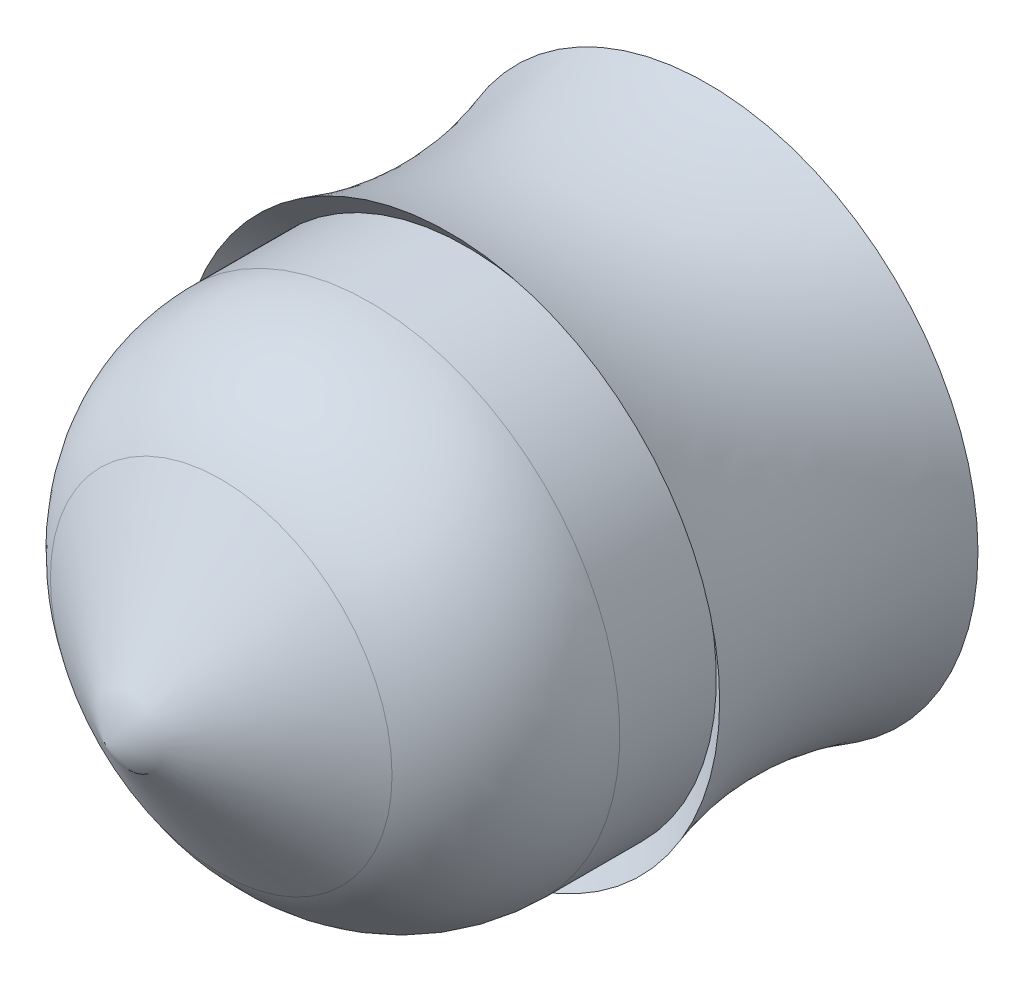
SolidWorks part; units mm, degrees
material "PE Vysoká hustota"
ref_plane "Horní rovina" through (0, 0, 0) normal (0, 0, 1) x (1, 0, 0)
ref_plane "Přední rovina" through (0, 0, 0) normal (0, 1, 0) x (1, 0, 0)
ref_plane "Pravá rovina" through (0, 0, 0) normal (1, 0, 0) x (0, 0, -1)
sketch "Skica1" plane through (0, 0, 0) normal (0, 0, 1) x (1, 0, 0)
  circle A0 centre (0, 0) radius 7.85
  dimension "D1" = 15.7
extrude "Přidat vysunutím1" add sketch "Skica1" along normal blind 7.5
sketch "Skica2" plane through (0, 0, 0) normal (0, 1, 0) x (1, 0, 0)
  line L0 (-7.85, -7.5) -> (7.85, -7.5) construction
  line L1 (-7.85, -7.5) -> (7.85, -7.5) construction
  line L2 (7.85, 0) -> (-7.85, 0) construction
  line L3 (7.85, 0) -> (-7.85, 0) construction
  line L4 (0, -14.5059) -> (0, 3.9252) construction
  line L5 (-7.85, -7.5) -> (-7.85, 0)
  arc A0 (-7.85, -7.5) -> (-7.85, 0) centre (-19.249, -3.75) ccw
  point P9 (-7.85, -3.75)
  dimension "D1" = 12
revolve "Odebrat rotací1" cut sketch "Skica2" angle 360 about L4
sketch "Skica4" plane through (0, 0, 0) normal (0, 1, 0) x (1, 0, 0)
  line L0 (-7.85, -7.5) -> (7.85, -7.5) construction
  line L1 (-7.85, -7.5) -> (7.85, -7.5) construction
  line L2 (0, 0) -> (0, -17.5) construction
  line L3 (0, -7.5) -> (-7.25, -7.5)
  line L4 (-7.25, -7.5) -> (-7.25, -9.8)
  line L5 (0, -17.5) -> (-4.961, -14.1254)
  line L6 (0, -17.5) -> (0, -7.5)
  arc A0 (-4.961, -14.1254) -> (-7.25, -9.8) centre (-2.0188, -9.8) cw
  dimension "D1" = 7.25
  dimension "D2" = 2.3
  dimension "D3" = 10
  dimension "D4" = 6
revolve "Rotovat1" add sketch "Skica4" angle 360 about L2
sketch "Skica5" plane through (0, 0, 0) normal (0, 1, 0) x (1, 0, 0)
  line L0 (-7.85, -7.5) -> (7.85, -7.5) construction
  line L1 (-7.85, -7.5) -> (7.85, -7.5) construction
  line L2 (-7.25, -7.5) -> (7.25, -7.5) construction
  line L3 (-7.25, -7.5) -> (7.25, -7.5) construction
  line L4 (-7.25, -7.5) -> (-7.25, -6.9965)
  line L5 (-7.25, -6.9965) -> (-7.85, -7.5)
  line L6 (-7.85, -7.5) -> (-7.25, -7.5)
  line L7 (0, 0) -> (0, -20.2146) construction
  dimension "D1" = 40
revolve "Odebrat rotací2" cut sketch "Skica5" angle 360 about L7
shell "Skořepina1" thickness 0.8 removed face at (7.85, 0, 0)
sketch "Skica6" plane through (0, 0, 0) normal (0, 0, 1) x (1, 0, 0)
  circle A0 centre (0, 0) radius 2
  dimension "D1" = 4
extrude "Přidat vysunutím2" add sketch "Skica6" along normal up to next from offset 9
sketch "Skica7" plane through (0, 0, 9) normal (0, 0, -1) x (-1, 0, 0)
  circle A0 centre (0, 0) radius 1
  dimension "D1" = 2
extrude "Odebrat vysunutím1" cut sketch "Skica7" against normal up to surface (6.8522 mm away) up to face at (-4.5111, 0, 13.4639)
sketch "Skica8" plane through (0, 0, 0) normal (0, 0, 1) x (1, 0, 0)
  line L0 (0, 0) -> (8.9804, 0) construction
  line L11 (1.9596, 0.4) -> (6.4376, 0.4)
  line L13 (1.9596, 0.4) -> (1.9596, -0.4) construction
  line L14 (1.9596, -0.4) -> (6.4376, -0.4)
  line L15 (6.4376, 0.4) -> (6.4376, -0.4) construction
  line L16 (1.9596, 0.4) -> (6.4376, -0.4) construction
  line L17 (1.9596, -0.4) -> (6.4376, 0.4) construction
  arc A0 (1.9596, -0.4) -> (1.9596, 0.4) centre (0, 0) ccw
  circle A4 centre (0, 0) radius 6.45 construction
  circle A7 centre (0, 0) radius 2 construction
  arc A8 (6.4376, -0.4) -> (6.4376, 0.4) centre (0, 0) ccw
  circle A12 centre (0, 0) radius 6.45 construction
  circle A13 centre (0, 0) radius 2 construction
  point P0 (4.1986, 0)
  dimension "D1" = 0.8
extrude "Přidat vysunutím7" add sketch "Skica8" along normal up to next from surface starting at face at (-1, 0, 9)
pattern_circular "Kruhové pole1" count 4 over 360 about axis through (0, 0, 9) along (0, 0, -1) of "Přidat vysunutím7"
sketch "Skica11" plane through (0, 0, 0) normal (0, 1, 0) x (1, 0, 0)
  line L0 (6.5376, -9.8) -> (6.5376, -9)
  line L3 (6.4376, -9.8) -> (6.4376, -9)
  line L4 (1.9596, -9) -> (1.9596, -15.172)
  line L5 (6.4376, -9) -> (1.9596, -9)
  line L6 (6.4376, -9.8) -> (6.4376, -9) construction
  line L7 (1.9596, -9) -> (1.9596, -15.172) construction
  line L8 (6.4376, -9) -> (1.9596, -9) construction
  line L9 (1.8596, -8.9) -> (1.8596, -15.36) construction
  line L10 (1.9596, -15.172) -> (4.4933, -13.4639) construction
  line L11 (1.8596, -15.36) -> (4.5493, -13.5467) construction
  line L12 (6.5376, -8.9) -> (1.8596, -8.9) construction
  line L13 (3.4596, -9) -> (6.1319, -11.6723)
  line L14 (3.4596, -9) -> (6.5376, -9)
  line L15 (6.5376, -9.8) -> (6.5376, -8.9) construction
  line L16 (0, 0) -> (0, -20.9939) construction
  spline S0 degree 1 poles (4.5493, -13.5467) (6.5376, -9.8) knots 0 0 1 1 construction
  spline S2 degree 3 poles (336.093, 3949.9235) (-368.0004, 250.9513) (-19.2767, -40.1177) (5.5441, -12.4898) (5.754, -12.1891) (6.0058, -11.7144) (6.08, -11.5514) (6.2088, -11.2154) (6.2636, -11.0414) (20.7742, 47.3659) (-1167.0022, 255.6626) (-3935.2453, 661.2338) knots -25.369542 -25.369542 -25.369542 -25.369542 0.25 0.25 0.5 0.5 0.625 0.625 0.75 0.75 42.34033 42.34033 42.34033 42.34033 only from (4.4933, -13.4639) to (6.4376, -9.8)
  spline S3 degree 3 poles (-2399.3678, 3177.3492) (2150.9174, -3378.5601) (-2142.0867, 3351.3669) (2407.3747, -3204.4617) knots -75.228616 -75.228616 -75.228616 -75.228616 77.085566 77.085566 77.085566 77.085566 only from (1.9596, -15.172) to (4.4933, -13.4639)
  spline S4 degree 3 poles (4.4933, -13.4639) (4.7936, -13.2604) (5.0644, -13.0237) (5.5441, -12.4898) (5.754, -12.1891) (6.0058, -11.7144) (6.08, -11.5514) (6.2088, -11.2154) (6.2636, -11.0414) (6.3941, -10.5163) (6.4376, -10.1609) (6.4376, -9.8) knots 0 0 0 0 0.25 0.25 0.5 0.5 0.625 0.625 0.75 0.75 1 1 1 1 construction
  spline S5 degree 3 poles (1.9596, -15.172) (2.8072, -14.6071) (3.6501, -14.0352) (4.4933, -13.4639) knots 0 0 0 0 1 1 1 1 construction
  spline S6 degree 3 poles (4.5493, -13.5467) (4.8529, -13.341) (5.4119, -12.8542) (6.0503, -11.9406) (6.448, -10.9009) (6.5376, -10.1662) (6.5376, -9.8) knots -0.000027 -0.000027 -0.000027 -0.000027 0.24998 0.499987 0.749993 1 1 1 1 only from (6.1319, -11.6723) to (6.5376, -9.8)
  dimension "D3" = 1.5
  dimension "D4" = 45
  dimension "D1" = 0
  dimension "D2" = 0.1
revolve "Odebrat rotací4" cut sketch "Skica11" angle 360 about L16
